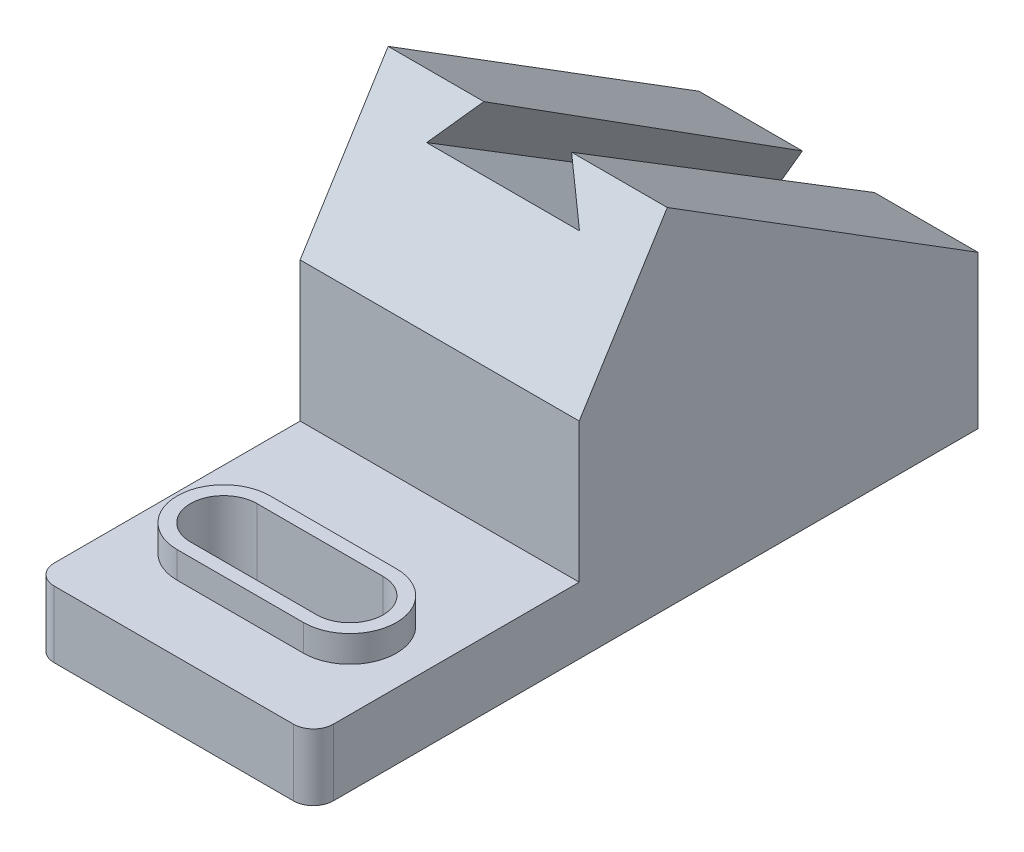
SolidWorks part; units mm, degrees
ref_plane "Front Plane" through (0, 0, 0) normal (0, 0, 1) x (1, 0, 0)
ref_plane "Top Plane" through (0, 0, 0) normal (0, 1, 0) x (1, 0, 0)
ref_plane "Right Plane" through (0, 0, 0) normal (1, 0, 0) x (0, 0, -1)
sketch "Sketch1" plane through (0, 0, 0) normal (1, 0, 0) x (0, 0, -1)
  line L0 (0, 0) -> (-100, 0)
  line L1 (-100, 0) -> (-100, 10)
  line L2 (-100, 10) -> (-60, 10)
  line L3 (-60, 10) -> (-60, 31)
  line L4 (-60, 31) -> (-46.752, 52.2012)
  line L5 (-46.752, 52.2012) -> (0, 22.9873)
  line L6 (0, 22.9873) -> (0, 0)
  point P6 (0, 0)
  dimension "D1" = 60
  dimension "D2" = 31
  dimension "D3" = 25
  dimension "D4" = 32
  dimension "D5" = 100
  dimension "D6" = 10
extrude "Boss-Extrude1" add sketch "Sketch1" along normal mid plane 42
sketch "Sketch2" plane through (0, 35.6691, 57.0824) normal (0, 0.5299, 0.848) x (1, 0, 0)
  line L0 (-5.8219, 20.6035) -> (-11.5, 12.4943)
  line L2 (-11.5, 12.4943) -> (11.5, 12.4943)
  line L3 (11.5, 12.4943) -> (5.8219, 20.6035)
  line L4 (0, 2.7784) -> (0, -1.5672) construction
  line L5 (21, 19.4943) -> (-21, 19.4943) construction
  line L6 (5.8219, 20.6035) -> (-5.8219, 20.6035)
  point P2 (-5.8219, 20.5867)
  point P9 (0, 0)
  line M8 (21, 19.4943) -> (-21, 19.4943)
  dimension "D1" = 55
  dimension "D2" = 23
  dimension "D3" = 7
extrude "Cut-Extrude1" cut sketch "Sketch2" against normal blind 60 draft 1 contours L2 L3 L0 M8 | L0 L2 L3 L6 region at (0, 48.9651, 48.7742)
sketch "Sketch3" plane through (0, 10, 0) normal (0, 1, 0) x (1, 0, 0)
  line L0 (-9.5, -83) -> (9.5, -83) construction
  line L1 (-9.5, -78) -> (9.5, -78)
  line L2 (-9.5, -88) -> (9.5, -88)
  line L3 (21, -100) -> (-21, -100) construction
  line L4 (-9.5, -76) -> (9.5, -76)
  line L5 (-9.5, -90) -> (9.5, -90)
  line L6 (-21, -60) -> (-21, -100) construction
  line L7 (21, -60) -> (21, -100) construction
  arc A0 (-9.5, -78) -> (-9.5, -88) centre (-9.5, -83) ccw
  arc A1 (9.5, -88) -> (9.5, -78) centre (9.5, -83) ccw
  arc A2 (9.5, -90) -> (9.5, -76) centre (9.5, -83) ccw
  arc A3 (-9.5, -76) -> (-9.5, -90) centre (-9.5, -83) ccw
  arc A4 (-21, -97) -> (-18, -100) centre (-18, -97) ccw
  arc A5 (21, -97) -> (18, -100) centre (18, -97) cw
  point P2 (0, -83)
  point P9 (0, -100)
  line M10 (-21, -60) -> (-21, -100)
  line M11 (-21, -100) -> (21, -100)
  line M12 (21, -100) -> (21, -60)
  dimension "D2" = 5
  dimension "D5" = 3
  dimension "D6" = 3
  dimension "D1" = 19
  dimension "D3" = 17
  dimension "D4" = 2
extrude "Cut-Extrude2" cut sketch "Sketch3" against normal up to next contours L2 A1 L1 A0 | A4 M10 M11 | A5 M12 M11 region at (0, 10, 83) region at (20.3299, 10, 99.3299) region at (-20.3299, 10, 99.3299)
extrude "Boss-Extrude2" add sketch "Sketch3<3>" along normal blind 4 contours L4 A3 L5 A2 A1 L2 A0 L1 region at (0, 10, 76.3585)
sketch "Sketch3<3>" plane through (0, 10, 0) normal (0, 1, 0) x (1, 0, 0) same geometry as "Sketch3"
